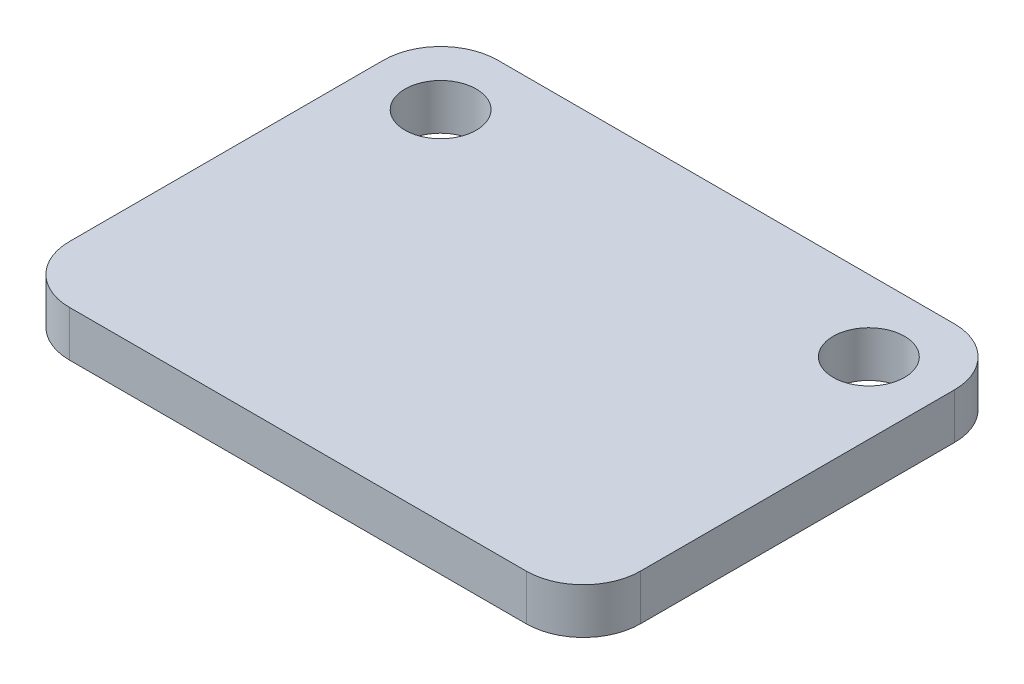
SolidWorks part; units mm, degrees
ref_plane "Front Plane" through (0, 0, 0) normal (0, 0, 1) x (1, 0, 0)
ref_plane "Top Plane" through (0, 0, 0) normal (0, 1, 0) x (1, 0, 0)
ref_plane "Right Plane" through (0, 0, 0) normal (1, 0, 0) x (0, 0, -1)
ref_axis "X" through (-88.99, 0, 0) along (1, 0, 0)
ref_axis "Y" through (0, 55, 0) along (0, -1, 0)
ref_axis "Z" through (0, 0, -88.99) along (0, 0, 1)
sketch "Sketch1" plane through (0, 0, 0) normal (0, 1, 0) x (1, 0, 0)
  line L0 (-7.5, 5) -> (7.5, 5) construction
  line L1 (-10, 7.5) -> (10, 7.5)
  line L2 (-10, 7.5) -> (-10, -7.5)
  line L3 (-10, -7.5) -> (10, -7.5)
  line L4 (10, 7.5) -> (10, -7.5)
  line L5 (-10, 7.5) -> (10, -7.5) construction
  line L6 (-10, -7.5) -> (10, 7.5) construction
  line L7 (0, 5) -> (0, 0) construction
  circle A0 centre (-7.5, 5) radius 1.25
  circle A1 centre (7.5, 5) radius 1.25
  point P0 (0, 0)
  dimension "D3" = 15
  dimension "D5" = 2.5
  dimension "D1" = 15
  dimension "D2" = 20
  dimension "D4" = 2.5
extrude "Boss-Extrude1" add sketch "Sketch1" along normal blind 1.6
fillet "Fillet1" radius 2 4 edges at (-10, 0.8, -7.5) (10, 0.8, -7.5) (10, 0.8, 7.5) (-10, 0.8, 7.5)
